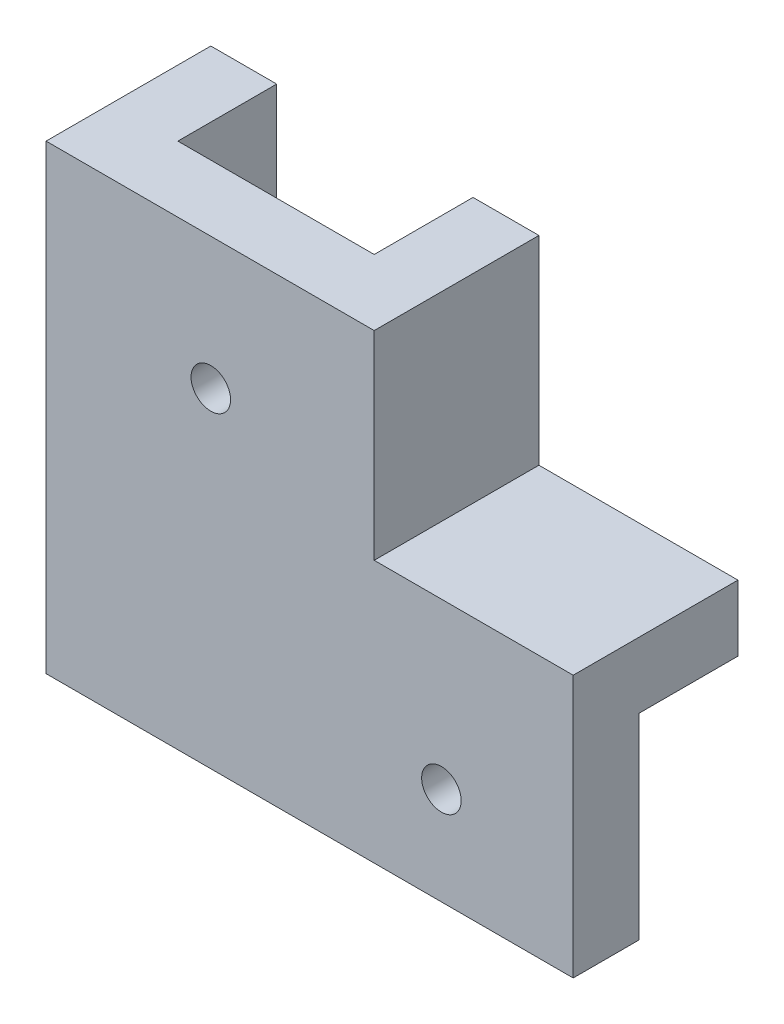
SolidWorks part; units mm, degrees
ref_plane "前视基准面" through (0, 0, 0) normal (0, 0, 1) x (1, 0, 0)
ref_plane "上视基准面" through (0, 0, 0) normal (0, 1, 0) x (1, 0, 0)
ref_plane "右视基准面" through (0, 0, 0) normal (1, 0, 0) x (0, 0, -1)
sketch "Sketch1" plane through (0, 0, 0) normal (0, 0, 1) x (1, 0, 0)
  line L0 (-7.5299, -25.8068) -> (27.4701, -25.8068)
  line L3 (-7.5299, 9.1932) -> (7.3701, 9.1932)
  line L4 (-7.5299, 9.1932) -> (-7.5299, -25.8068)
  line L6 (7.3701, 9.1932) -> (7.3701, -10.9068)
  line L7 (27.4701, -25.8068) -> (27.4701, -10.9068)
  line L8 (27.4701, -10.9068) -> (7.3701, -10.9068)
  dimension "D1" = 14.9
  dimension "D2" = 35
  dimension "D3" = 35
  dimension "D4" = 14.9
extrude "Boss-Extrude1" add sketch "Sketch1" along normal blind 5
sketch "Sketch2" plane through (0, 0, 0) normal (0, 0, -1) x (-1, 0, 0)
  line L0 (-7.3701, 9.1932) -> (-12.3701, 9.1932)
  line L1 (-12.3701, 9.1932) -> (-12.3701, -5.9068)
  line L2 (-12.3701, -5.9068) -> (-27.4701, -5.9068)
  line L3 (-27.4701, -10.9068) -> (-27.4701, -5.9068)
  line L4 (-27.4701, -10.9068) -> (-7.3701, -10.9068)
  line L5 (-7.3701, -10.9068) -> (-7.3701, 9.1932)
  dimension "D1" = 5
  dimension "D2" = 5
extrude "Boss-Extrude2" add sketch "Sketch2" along normal blind 7.5 separate body
sketch "Sketch3" plane through (0, 0, 0) normal (0, 0, -1) x (-1, 0, 0)
  line L0 (7.5299, 9.1932) -> (12.5299, 9.1932)
  line L1 (7.5299, -25.8068) -> (12.5299, -25.8068)
  line L2 (12.5299, -25.8068) -> (12.5299, 9.1932)
  line L3 (7.5299, -25.8068) -> (7.5299, 9.1932)
  dimension "D1" = 5
extrude "Boss-Extrude3" add sketch "Sketch3" along normal blind 7.5 separate body
sketch "Sketch4" plane through (0, 0, 0) normal (0, 0, 1) x (1, 0, 0)
  line L1 (-12.5299, 9.1932) -> (-7.5299, 9.1932)
  line L2 (-12.5299, 9.1932) -> (-12.5299, -25.8068)
  line L3 (-12.5299, -25.8068) -> (-7.5299, -25.8068)
  line L4 (-7.5299, 9.1932) -> (-7.5299, -25.8068)
extrude "Boss-Extrude4" add sketch "Sketch4" along normal blind 5
sketch "Sketch5" plane through (0, 0, 0) normal (0, 0, 1) x (1, 0, 0)
  line L0 (7.3701, 9.1932) -> (7.3701, -10.9068)
  line L1 (7.3701, -10.9068) -> (27.4701, -10.9068)
  line L2 (27.4701, -10.9068) -> (27.4701, -5.9068)
  line L3 (27.4701, -5.9068) -> (12.3701, -5.9068)
  line L4 (12.3701, -5.9068) -> (12.3701, 9.1932)
  line L5 (12.3701, 9.1932) -> (7.3701, 9.1932)
extrude "Boss-Extrude5" add sketch "Sketch5" along normal blind 5
sketch "Sketch7" plane through (0, 0, 0) normal (0, 0, -1) x (-1, 0, 0)
  line L0 (-27.4701, -25.8068) -> (-27.4701, -10.9068) construction
  line L1 (-27.4701, -10.9068) -> (-7.3701, -10.9068) construction
  line L2 (-7.3701, 9.1932) -> (7.5299, 9.1932) construction
  line L3 (7.5299, 9.1932) -> (7.5299, -25.8068) construction
  circle A0 centre (0.0299, -0.8068) radius 1.5
  circle A1 centre (-17.4701, -18.4068) radius 1.5
  dimension "D1" = 3
  dimension "D2" = 3
  dimension "D3" = 10
  dimension "D5" = 10
  dimension "D6" = 7.5
  dimension "D4" = 7.5
extrude "Cut-Extrude1" cut sketch "Sketch7" against normal through all
